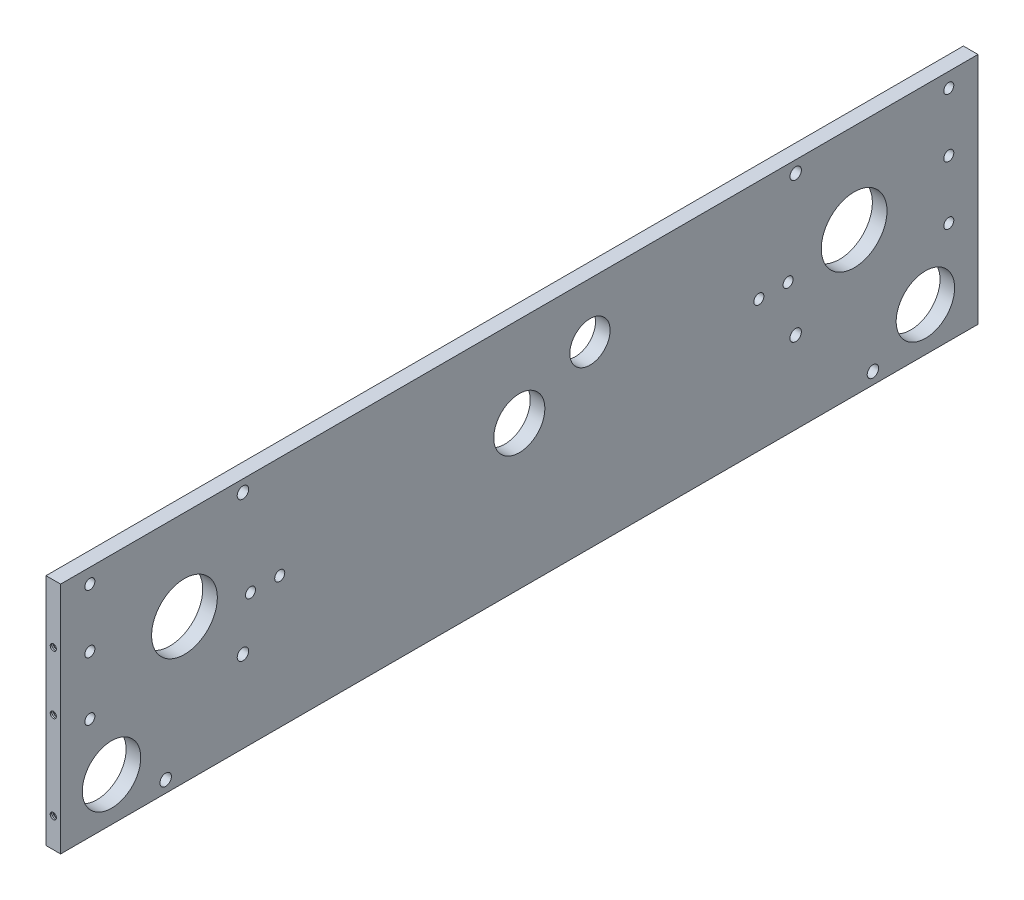
SolidWorks part; units mm, degrees
material "6061-T6 (SS)"
ref_plane "Front Plane" through (0, 0, 0) normal (0, 0, 1) x (1, 0, 0)
ref_plane "Top Plane" through (0, 0, 0) normal (0, 1, 0) x (1, 0, 0)
ref_plane "Right Plane" through (0, 0, 0) normal (1, 0, 0) x (0, 0, -1)
sketch "Sketch1" plane through (0, 0, 0) normal (1, 0, 0) x (0, 0, -1)
  line L1 (-199.39, 50.8) -> (199.39, 50.8)
  line L2 (-199.39, 50.8) -> (-199.39, -50.8)
  line L3 (-199.39, -50.8) -> (199.39, -50.8)
  line L4 (199.39, 50.8) -> (199.39, -50.8)
  line L5 (-199.39, 50.8) -> (199.39, -50.8) construction
  line L6 (-199.39, -50.8) -> (199.39, 50.8) construction
  point P0 (0, 0)
  dimension "D1" = 101.6
  dimension "D2" = 398.78
extrude "Boss-Extrude1" add sketch "Sketch1" along normal blind 6.35
sketch "Sketch2" plane through (6.35, 0, 0) normal (1, 0, 0) x (0, 0, -1)
  line L0 (-199.39, -50.8) -> (199.39, -50.8) construction
  line L1 (-145.5447, 11.6882) -> (0, 11.6882) construction
  line L2 (199.39, 50.8) -> (-199.39, 50.8) construction
  line L3 (0, 11.6882) -> (145.5447, 11.6882) construction
  line L4 (1.4287, 28.7746) -> (-143.1055, 40.86) construction
  line L5 (1.4287, -5.3983) -> (-143.1055, -17.4837) construction
  line L10 (0.9292, 22.8011) -> (-143.605, 34.8865) construction
  line L11 (-199.39, 50.8) -> (-199.39, -50.8) construction
  line L15 (0, -50.8) -> (0, -20.32) construction
  line L16 (199.39, -50.8) -> (199.39, 50.8) construction
  line L17 (-163.0212, -41.4951) -> (-132.9859, 3.2599) construction
  line L18 (0.9292, 0.5753) -> (-143.605, -11.5102) construction
  line L19 (-177.2583, -31.9405) -> (-199.39, -31.9405) construction
  line L20 (-177.2583, -31.9405) -> (-158.1418, -43.0925) construction
  line L23 (-120.1014, -15.5602) -> (-120.5589, -10.0878) construction
  line L24 (-120.5589, 40.5678) -> (-120.6912, 38.9858) construction
  circle A1 centre (-145.5447, 11.6882) radius 14.2875
  circle A2 centre (145.5447, 11.6882) radius 14.2875
  circle A3 centre (-145.5447, 11.6882) radius 29.2737 construction
  circle A4 centre (0, 11.6882) radius 30.48 construction
  circle A5 centre (145.5447, 11.6882) radius 29.2737 construction
  circle A11 centre (-177.2583, -31.9405) radius 12.7
  circle A12 centre (176.53, -31.9405) radius 12.7
  circle A13 centre (0, 11.6882) radius 11.1125
  circle A14 centre (-177.2583, -31.9405) radius 20.6375 construction
  circle A15 centre (-177.2583, -31.9405) radius 17.1461 construction
  circle A16 centre (-145.5447, 11.6882) radius 15.1248 construction
  circle A17 centre (0, 11.6882) radius 17.1461 construction
  circle A18 centre (34.3662, 11.6882) radius 8.7754 construction
  circle A19 centre (-153.715, -45.675) radius 5.125 construction
  circle A20 centre (-153.715, -45.675) radius 2.4892
  circle A21 centre (-120.1319, 45.675) radius 5.125 construction
  circle A22 centre (-120.1319, -15.195) radius 5.125 construction
  circle A23 centre (-120.1319, -15.195) radius 2.4892
  circle A24 centre (-120.1319, 45.675) radius 2.4892
  circle A25 centre (120.1319, 45.675) radius 2.4892
  circle A26 centre (120.1319, -15.195) radius 2.4892
  circle A27 centre (153.715, -45.675) radius 2.4892
  circle A28 centre (0, 11.6882) radius 29.21 construction
  circle A29 centre (30.7172, 26.9282) radius 5.08 construction
  circle A30 centre (30.7172, 26.9282) radius 8.75
  point P11 (0, 0)
  point P12 (0, -18.7918)
  point P14 (0, 42.1682)
  point P52 (-197.8958, -31.9405)
  point P56 (-159.8322, 11.6882)
  dimension "D1" = 28.575
  dimension "D5" = 58.5474
  dimension "D7" = 8.6318
  dimension "D14" = 25.4
  dimension "D15" = 53.9371
  dimension "D17" = 25.4
  dimension "D20" = 22.225
  dimension "D21" = 28.575
  dimension "D22" = 60.96
  dimension "D23" = 41.275
  dimension "D27" = 34.2921
  dimension "D28" = 30.2496
  dimension "D12" = 17.5508
  dimension "D13" = 10.25
  dimension "D29" = 4.9784
  dimension "D26" = 1.5875
  dimension "D30" = 4.9784
  dimension "D31" = 58.42
  dimension "D32" = 10.16
  dimension "D33" = 17.5001
  dimension "D3" = 39.5578
  dimension "D4" = 145.5447
  dimension "D6" = 0
  dimension "D9" = 5.9944
  dimension "D10" = 5.9944
  dimension "D11" = 34.3662
  dimension "D16" = 1.4942
  dimension "D18" = 18.8595
  dimension "D19" = 22.86
  dimension "D24" = 30.48
  dimension "D34" = 15.24
extrude "Cut-Extrude1" cut sketch "Sketch2" against normal through all
sketch "Sketch3" plane through (6.35, 0, 0) normal (1, 0, 0) x (0, 0, -1)
  line L0 (-193.294, 19.05) -> (-193.294, -19.05) construction
  line L1 (-199.39, 50.8) -> (-199.39, -50.8) construction
  point P2 (-193.294, 0)
  point P3 (-199.39, 0)
  dimension "D1" = 38.1
  dimension "D2" = 6.096
sketch "Sketch27" plane through (0, 0, -199.39) normal (0, 0, -1) x (-1, 0, 0)
  line L0 (-6.35, 50.8) -> (0, 50.8) construction
  line L1 (-6.35, -50.8) -> (-6.35, 50.8) construction
  point P0 (-3.175, 25.4)
  point P1 (-3.175, 0)
  point P2 (-3.175, -38.1)
  dimension "D1" = 25.4
  dimension "D2" = 3.175
hole_wizard "#36 (0.1065) Diameter Hole2" positions "Sketch28" profile "Sketch29" hole size "#36" standard "ANSI Inch"
sketch "Sketch28" plane through (0, 0, -199.39) normal (0, 0, -1) x (-1, 0, 0)
  point P0 (-3.175, 25.4)
  point P3 (-3.175, 0)
  point P6 (-3.175, -38.1)
sketch "Sketch29" plane through (3.175, 25.4, -199.39) normal (1, 0, 0) x (0, 1, 0)
  line L0 (0, 0) -> (0, 9.7027)
  line L1 (0, 9.7027) -> (1.3525, 8.89)
  line L2 (1.3525, 8.89) -> (1.3525, 0)
  line L5 (1.3525, 0) -> (0, 0)
  line L10 (0, 9.7027) -> (-1.3526, 8.89) construction
  line L11 (0, -6.35) -> (0, 107.95) construction
  dimension "Hole Dia." = 2.7051
  dimension "Hole Depth" = 8.89
  dimension "Drill Angle" = 118
thread "Thread3" pitch 0.7937 method cut profile "Thread Profile3" start angle 0, offset 0, length 6.35, pitch 0.7937, diameter 2.7051
ref_plane "Plane3" through (4.5275, 25.4, -199.39) normal (0, -1, 0) x (1, 0, 0)
sketch "Thread Profile3" plane through (4.5275, 25.4, -199.39) normal (0, -1, 0) x (1, 0, 0)
  line L0 (0, 0) -> (0, 0.7937) construction
  line L1 (0, 0) -> (0.4296, 0.248)
  line L2 (0.4296, 0.248) -> (0.4296, 0.3473)
  line L3 (0.4296, 0.3473) -> (0, 0.5953)
  line L4 (0.4296, 0.2977) -> (0, 0.2977) construction
  line L11 (0, 0) -> (0, 0.5953)
  point P2 (0, 0)
  dimension "Pitch" = 0.7937
  dimension "Profile_Angle" = 60
  dimension "Profile_Land" = 0.0992
  dimension "Profile_Height" = 0.4296
thread "Thread4" pitch 0.7937 method cut profile "Thread Profile4" start angle 0, offset 0, length 6.35, pitch 0.7937, diameter 2.7051
ref_plane "Plane4" through (4.5275, 0, -199.39) normal (0, -1, 0) x (1, 0, 0)
sketch "Thread Profile4" plane through (4.5275, 0, -199.39) normal (0, -1, 0) x (1, 0, 0)
  line L0 (0, 0) -> (0, 0.7937) construction
  line L1 (0, 0) -> (0.4296, 0.248)
  line L2 (0.4296, 0.248) -> (0.4296, 0.3473)
  line L3 (0.4296, 0.3473) -> (0, 0.5953)
  line L4 (0.4296, 0.2977) -> (0, 0.2977) construction
  line L11 (0, 0) -> (0, 0.5953)
  point P2 (0, 0)
  dimension "Pitch" = 0.7937
  dimension "Profile_Angle" = 60
  dimension "Profile_Land" = 0.0992
  dimension "Profile_Height" = 0.4296
thread "Thread5" pitch 0.7937 method cut profile "Thread Profile5" start angle 0, offset 0, length 6.35, pitch 0.7937, diameter 2.7051
ref_plane "Plane5" through (4.5275, -38.1, -199.39) normal (0, -1, 0) x (1, 0, 0)
sketch "Thread Profile5" plane through (4.5275, -38.1, -199.39) normal (0, -1, 0) x (1, 0, 0)
  line L0 (0, 0) -> (0, 0.7937) construction
  line L1 (0, 0) -> (0.4296, 0.248)
  line L2 (0.4296, 0.248) -> (0.4296, 0.3473)
  line L3 (0.4296, 0.3473) -> (0, 0.5953)
  line L4 (0.4296, 0.2977) -> (0, 0.2977) construction
  line L11 (0, 0) -> (0, 0.5953)
  point P2 (0, 0)
  dimension "Pitch" = 0.7937
  dimension "Profile_Angle" = 60
  dimension "Profile_Land" = 0.0992
  dimension "Profile_Height" = 0.4296
sketch "Sketch36" plane through (0, 0, 199.39) normal (0, 0, 1) x (1, 0, 0)
  line L0 (6.35, 50.8) -> (6.35, -50.8) construction
  line L1 (6.35, 50.8) -> (0, 50.8) construction
  point P0 (3.175, 25.4)
  point P1 (3.175, -12.7)
  point P2 (3.175, -50.8)
  dimension "D1" = 25.4
  dimension "D2" = 3.175
  dimension "D3" = 38.1
  dimension "D4" = 38.1
hole_wizard "#36 (0.1065) Diameter Hole3" positions "Sketch37" profile "Sketch38" hole size "#36" standard "ANSI Inch"
sketch "Sketch37" plane through (0, 0, 199.39) normal (0, 0, 1) x (1, 0, 0)
  point P0 (3.175, 25.4)
  point P3 (3.175, 0)
  point P6 (3.175, -38.1)
sketch "Sketch38" plane through (3.175, 25.4, 199.39) normal (1, 0, 0) x (0, -1, 0)
  line L0 (0, 0) -> (0, 9.7027)
  line L1 (0, 9.7027) -> (1.3525, 8.89)
  line L2 (1.3525, 8.89) -> (1.3525, 0)
  line L5 (1.3525, 0) -> (0, 0)
  line L10 (0, 9.7027) -> (-1.3525, 8.89) construction
  line L11 (0, -6.35) -> (0, 107.95) construction
  dimension "Hole Dia." = 2.7051
  dimension "Hole Depth" = 8.89
  dimension "Drill Angle" = 118
thread "Thread6" pitch 0.7937 method cut profile "Thread Profile6" start angle 0, offset 0, length 6.35, pitch 0.7937, diameter 2.7051
ref_plane "Plane6" through (1.8225, 25.4, 199.39) normal (0, -1, 0) x (-1, 0, 0)
sketch "Thread Profile6" plane through (1.8225, 25.4, 199.39) normal (0, -1, 0) x (-1, 0, 0)
  line L0 (0, 0) -> (0, 0.7937) construction
  line L1 (0, 0) -> (0.4296, 0.248)
  line L2 (0.4296, 0.248) -> (0.4296, 0.3473)
  line L3 (0.4296, 0.3473) -> (0, 0.5953)
  line L4 (0.4296, 0.2977) -> (0, 0.2977) construction
  line L11 (0, 0) -> (0, 0.5953)
  point P2 (0, 0)
  dimension "Pitch" = 0.7937
  dimension "Profile_Angle" = 60
  dimension "Profile_Land" = 0.0992
  dimension "Profile_Height" = 0.4296
thread "Thread7" pitch 0.7937 method cut profile "Thread Profile7" start angle 0, offset 0, length 6.35, pitch 0.7937, diameter 2.7051
ref_plane "Plane7" through (1.8225, 0, 199.39) normal (0, -1, 0) x (-1, 0, 0)
sketch "Thread Profile7" plane through (1.8225, 0, 199.39) normal (0, -1, 0) x (-1, 0, 0)
  line L0 (0, 0) -> (0, 0.7937) construction
  line L1 (0, 0) -> (0.4296, 0.248)
  line L2 (0.4296, 0.248) -> (0.4296, 0.3473)
  line L3 (0.4296, 0.3473) -> (0, 0.5953)
  line L4 (0.4296, 0.2977) -> (0, 0.2977) construction
  line L11 (0, 0) -> (0, 0.5953)
  point P2 (0, 0)
  dimension "Pitch" = 0.7937
  dimension "Profile_Angle" = 60
  dimension "Profile_Land" = 0.0992
  dimension "Profile_Height" = 0.4296
thread "Thread8" pitch 0.7937 method cut profile "Thread Profile8" start angle 0, offset 0, length 6.35, pitch 0.7937, diameter 2.7051
ref_plane "Plane8" through (1.8225, -38.1, 199.39) normal (0, -1, 0) x (-1, 0, 0)
sketch "Thread Profile8" plane through (1.8225, -38.1, 199.39) normal (0, -1, 0) x (-1, 0, 0)
  line L0 (0, 0) -> (0, 0.7937) construction
  line L1 (0, 0) -> (0.4296, 0.248)
  line L2 (0.4296, 0.248) -> (0.4296, 0.3473)
  line L3 (0.4296, 0.3473) -> (0, 0.5953)
  line L4 (0.4296, 0.2977) -> (0, 0.2977) construction
  line L11 (0, 0) -> (0, 0.5953)
  point P2 (0, 0)
  dimension "Pitch" = 0.7937
  dimension "Profile_Angle" = 60
  dimension "Profile_Land" = 0.0992
  dimension "Profile_Height" = 0.4296
sketch "Sketch40" plane through (6.35, 0, 0) normal (1, 0, 0) x (0, 0, -1)
  line L0 (199.39, 50.8) -> (-199.39, 50.8) construction
  line L5 (-199.39, 50.8) -> (-199.39, -50.8) construction
  line L6 (199.39, -50.8) -> (199.39, 50.8) construction
  line L7 (-199.39, -50.8) -> (199.39, -50.8) construction
  point P2 (186.69, -6.35)
  point P3 (186.69, 19.05)
  point P4 (186.69, 44.45)
  point P7 (-186.69, -6.35)
  point P8 (-186.69, 19.05)
  point P9 (-186.69, 44.45)
  dimension "D2" = 12.7
  dimension "D3" = 25.4
  dimension "D4" = 25.4
  dimension "D5" = 6.35
  dimension "D6" = 25.4
  dimension "D7" = 25.4
  dimension "D8" = 44.45
  dimension "D10" = 12.7
hole_wizard "11/64 (0.17188) Diameter Hole1" positions "Sketch41" profile "Sketch43" hole size "11/64" standard "ANSI Inch" end condition through all
sketch "Sketch41" plane through (6.35, 0, 0) normal (1, 0, 0) x (0, 0, -1)
  point P0 (-186.69, 44.45)
  point P3 (-186.69, 19.05)
  point P6 (-186.69, -6.35)
  point P9 (186.69, -6.35)
  point P12 (186.69, 19.05)
  point P15 (186.69, 44.45)
sketch "Sketch43" plane through (6.35, 44.45, 186.69) normal (0, 1, 0) x (0, 0, -1)
  line L0 (0, 0) -> (0, 6.35)
  line L1 (0, 6.35) -> (2.1829, 6.35)
  line L2 (2.1829, 6.35) -> (2.1829, 0)
  line L5 (2.1829, 0) -> (0, 0)
  line L11 (0, -6.35) -> (0, 107.95) construction
  dimension "Thru Hole Dia." = 4.3658
  dimension "Thru Hole Depth" = 6.35
sketch "Sketch44" plane through (6.35, 0, 0) normal (1, 0, 0) x (0, 0, -1)
  line L0 (-199.39, 50.8) -> (-199.39, -50.8) construction
  line L1 (199.39, 50.8) -> (-199.39, 50.8) construction
  line L2 (199.39, -50.8) -> (199.39, 50.8) construction
  point P0 (-116.84, 6.35)
  point P1 (116.84, 6.35)
  point P8 (-104.14, 6.35)
  point P9 (104.14, 6.35)
  dimension "D1" = 82.55
  dimension "D2" = 44.45
  dimension "D3" = 82.55
  dimension "D4" = 12.7
  dimension "D5" = 12.7
hole_wizard "11/64 (0.17188) Diameter Hole2" positions "Sketch45" profile "Sketch46" hole size "11/64" standard "ANSI Inch" end condition through all
sketch "Sketch45" plane through (6.35, 0, 0) normal (1, 0, 0) x (0, 0, -1)
  point P0 (-116.84, 6.35)
  point P3 (116.84, 6.35)
  point P6 (-104.14, 6.35)
  point P9 (104.14, 6.35)
sketch "Sketch46" plane through (6.35, 6.35, 116.84) normal (0, 1, 0) x (0, 0, -1)
  line L0 (0, 0) -> (0, 6.35)
  line L1 (0, 6.35) -> (2.1829, 6.35)
  line L2 (2.1829, 6.35) -> (2.1829, 0)
  line L5 (2.1829, 0) -> (0, 0)
  line L11 (0, -6.35) -> (0, 107.95) construction
  dimension "Thru Hole Dia." = 4.3658
  dimension "Thru Hole Depth" = 6.35
